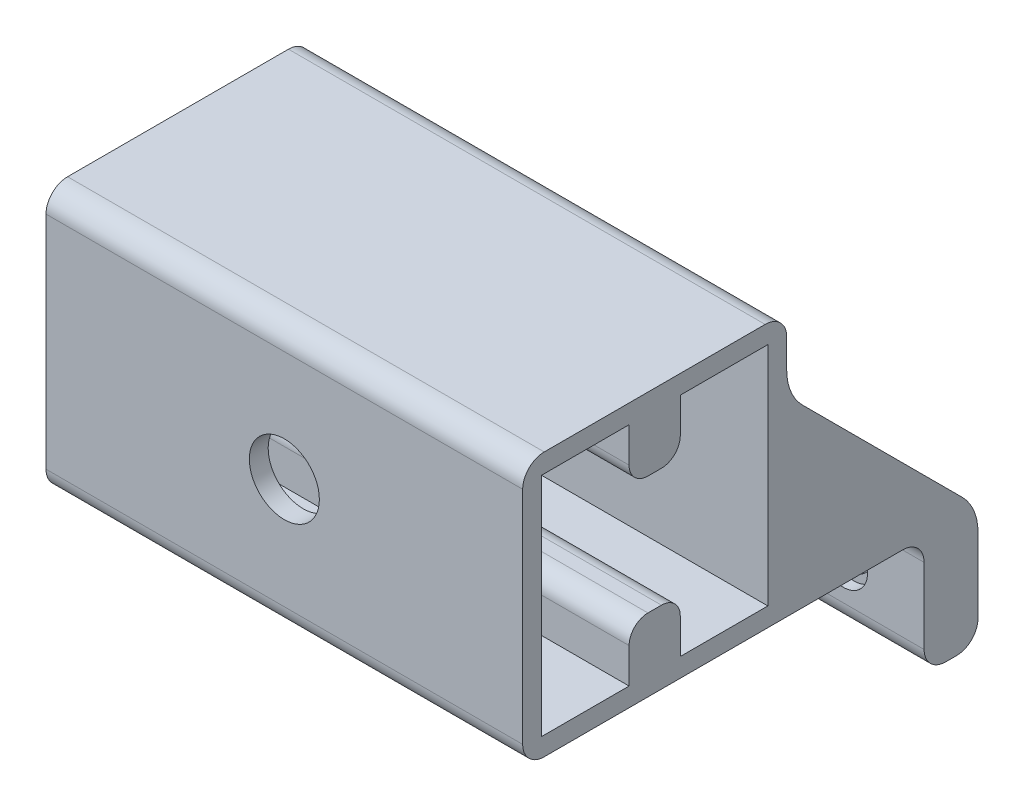
SolidWorks part; units mm, degrees
ref_plane "Front Plane" through (0, 0, 0) normal (0, 0, 1) x (1, 0, 0)
ref_plane "Top Plane" through (0, 0, 0) normal (0, 1, 0) x (1, 0, 0)
ref_plane "Right Plane" through (0, 0, 0) normal (1, 0, 0) x (0, 0, -1)
sketch "Sketch1" plane through (0, 0, 0) normal (1, 0, 0) x (0, 0, -1)
  line L0 (0, 0) -> (4.6501, 0) construction
  line L1 (-10.5, -10.5) -> (10.5, -10.5)
  line L2 (-10.5, -10.5) -> (-10.5, 10.5)
  line L3 (-10.5, 10.5) -> (10.5, 10.5)
  line L4 (10.5, -10.5) -> (10.5, 10.5)
  line L5 (-10.5, -10.5) -> (10.5, 10.5) construction
  line L6 (-10.5, 10.5) -> (10.5, -10.5) construction
  line L7 (-0.625, 5.5) -> (0.625, 5.5)
  line L8 (-2.375, 7.25) -> (-2.375, 10.5)
  line L10 (2.375, 7.25) -> (2.375, 10.5)
  line L11 (-2.375, 5.5) -> (0, 10.5) construction
  line L12 (0, 10.5) -> (2.375, 5.5) construction
  line L13 (2.375, -7.25) -> (2.375, -10.5)
  line L14 (-0.625, -5.5) -> (0.625, -5.5)
  line L15 (-2.375, -7.25) -> (-2.375, -10.5)
  line L16 (12.25, -12.25) -> (23, -12.25)
  line L17 (-10.25, -12.25) -> (12.25, -12.25)
  line L18 (-12.25, -10.25) -> (-12.25, 10.25)
  line L19 (-10.25, 12.25) -> (10.25, 12.25)
  line L20 (12.25, 7.5711) -> (12.25, 10.25)
  line L21 (-12.25, -12.25) -> (12.25, 12.25) construction
  line L22 (-12.25, 12.25) -> (12.25, -12.25) construction
  line L23 (28.5355, -10.7855) -> (13.7145, 4.0355)
  line L24 (25, -12.25) -> (30, -12.25)
  line L25 (25, -14.25) -> (25, -21.25)
  line L26 (27, -23.25) -> (28, -23.25)
  line L27 (30, -14.3211) -> (30, -21.25)
  arc A0 (0.625, 5.5) -> (2.375, 7.25) centre (0.625, 7.25) ccw
  arc A1 (-0.625, 5.5) -> (-2.375, 7.25) centre (-0.625, 7.25) cw
  arc A2 (0.625, -5.5) -> (2.375, -7.25) centre (0.625, -7.25) cw
  arc A3 (-0.625, -5.5) -> (-2.375, -7.25) centre (-0.625, -7.25) ccw
  arc A4 (10.25, 12.25) -> (12.25, 10.25) centre (10.25, 10.25) cw
  arc A5 (-10.25, -12.25) -> (-12.25, -10.25) centre (-10.25, -10.25) cw
  arc A6 (-12.25, 10.25) -> (-10.25, 12.25) centre (-10.25, 10.25) cw
  arc A7 (25, -14.25) -> (23, -12.25) centre (23, -14.25) ccw
  arc A8 (28, -23.25) -> (30, -21.25) centre (28, -21.25) ccw
  arc A9 (25, -21.25) -> (27, -23.25) centre (27, -21.25) ccw
  arc A10 (30, -14.3211) -> (28.5355, -10.7855) centre (25, -14.3211) ccw
  arc A11 (13.7145, 4.0355) -> (12.25, 7.5711) centre (17.25, 7.5711) cw
  point P0 (0, 0)
  point P6 (0, 10.5)
  point P51 (30, -23.25)
  point P54 (25, -23.25)
  dimension "D5" = 1.75
  dimension "D8" = 2
  dimension "D12" = 2
  dimension "D13" = 5
  dimension "D1" = 21
  dimension "D2" = 21
  dimension "D3" = 4.75
  dimension "D4" = 5
  dimension "D6" = 24.5
  dimension "D7" = 24.5
  dimension "D10" = 11
  dimension "D11" = 5
extrude "Boss-Extrude1" add sketch "Sketch1" along normal blind 22.115 and the other way blind 22.115 contours L23 A11 L20 A4 L19 A6 L18 A5 L17 L16 A7 L25 A9 L26 A8 L27 A10 L4 L1 L2 L3 | L14 A3 L15 L1 L13 A2 | A1 L7 A0 L10 L3 L8 region at (0, -8.1236, 0) region at (0, 8.1236, 0) region at (0, -5.2835, -11.807)
sketch "Sketch2" plane through (0, 0, 12.25) normal (0, 0, 1) x (1, 0, 0)
  circle A0 centre (0, 0) radius 3.25
extrude "Cut-Extrude1" cut sketch "Sketch2" against normal blind 11.115
sketch "Sketch3" plane through (0, 0, -25) normal (0, 0, 1) x (1, 0, 0)
  line L0 (22.115, -17.75) -> (14.615, -17.75) construction
  line L1 (22.115, -14.25) -> (22.115, -21.25) construction
  line L2 (14.615, -17.75) -> (-5.385, -17.75) construction
  circle A0 centre (14.615, -17.75) radius 2.25
  circle A1 centre (-5.385, -17.75) radius 2.25
  dimension "D1" = 7.5
  dimension "D3" = 4.5
  dimension "D4" = 4.5
  dimension "D2" = 20
extrude "Cut-Extrude2" cut sketch "Sketch3" against normal blind 1 contours A1 | A0
sketch "Sketch4" plane through (0, 0, -26) normal (0, 0, 1) x (1, 0, 0)
  circle A0 centre (-5.385, -17.75) radius 1.5
  circle A1 centre (14.615, -17.75) radius 1.5
extrude "Cut-Extrude3" cut sketch "Sketch4" against normal blind 6 contours A0 | A1
